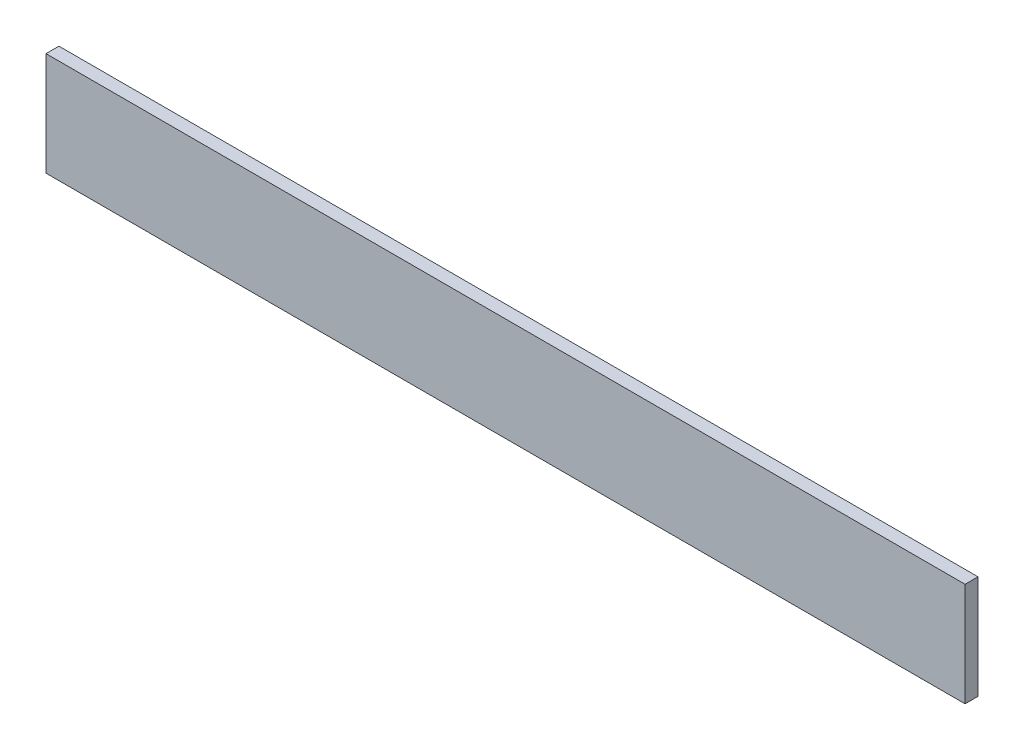
SolidWorks part; units mm, degrees
material "ABS"
ref_plane "X-Y Datum" through (0, 0, 0) normal (0, 0, 1) x (1, 0, 0)
ref_plane "X-Z Datum" through (0, 0, 0) normal (0, 1, 0) x (1, 0, 0)
ref_plane "Y-Z Datum" through (0, 0, 0) normal (1, 0, 0) x (0, 0, -1)
sketch "Sketch1" plane through (0, 0, 0) normal (0, 0, 1) x (1, 0, 0)
  line L1 (-225.435, -25.4) -> (225.435, -25.4)
  line L2 (-225.435, -25.4) -> (-225.435, 25.4)
  line L3 (-225.435, 25.4) -> (225.435, 25.4)
  line L4 (225.435, -25.4) -> (225.435, 25.4)
  line L5 (-225.435, -25.4) -> (225.435, 25.4) construction
  line L6 (-225.435, 25.4) -> (225.435, -25.4) construction
  point P0 (0, 0)
  dimension "D1" = 450.87
  dimension "D2" = 50.8
extrude "Boss-Extrude1" add sketch "Sketch1" along normal blind 6.35
